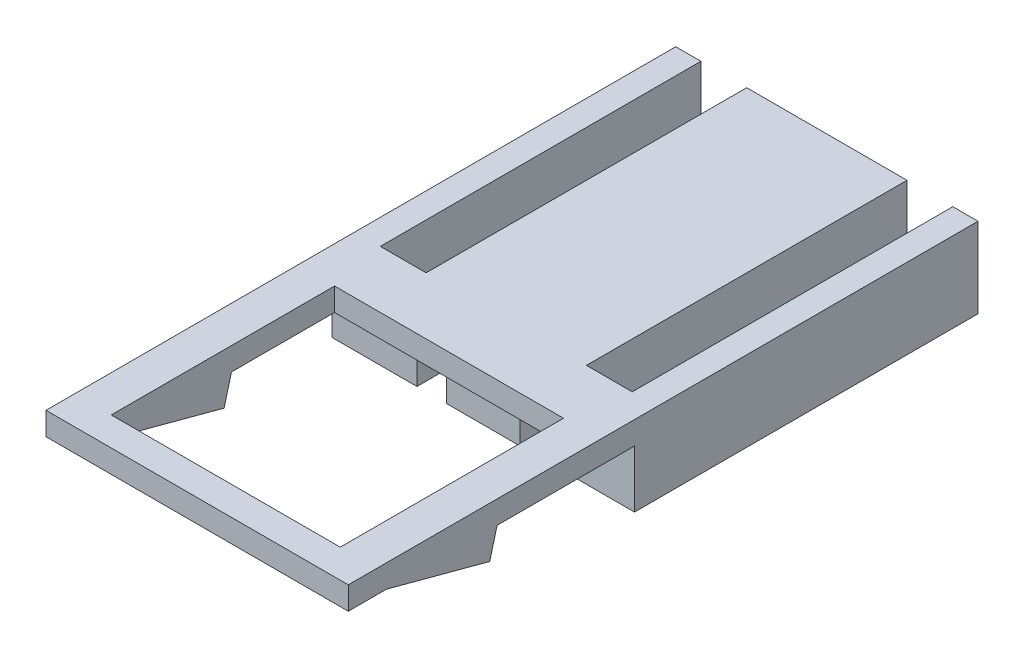
SolidWorks part; units mm, degrees
ref_plane "Front Plane" through (0, 0, 0) normal (0, 0, 1) x (1, 0, 0)
ref_plane "Top Plane" through (0, 0, 0) normal (0, 1, 0) x (1, 0, 0)
ref_plane "Right Plane" through (0, 0, 0) normal (1, 0, 0) x (0, 0, -1)
sketch "Sketch1" plane through (0, 0, 0) normal (0, 1, 0) x (1, 0, 0)
  line L1 (-31.75, 35) -> (31.75, 35)
  line L2 (-31.75, 35) -> (-31.75, 0)
  line L3 (-31.75, 0) -> (31.75, 0)
  line L4 (31.75, 35) -> (31.75, 0)
extrude "Boss-Extrude1" add sketch "Sketch1" along normal blind 12
sketch "Sketch3" plane through (0, 0, 0) normal (0, -1, 0) x (1, 0, 0)
  line L0 (-31.75, 0) -> (31.75, 0) construction
  line L1 (-13.2, 0) -> (13.2, 0)
  line L2 (-13.2, 0) -> (-13.2, -35)
  line L3 (-13.2, -35) -> (13.2, -35)
  line L4 (13.2, 0) -> (13.2, -35)
  line L5 (31.75, -35) -> (-31.75, -35) construction
extrude "Cut-Extrude2" cut sketch "Sketch3" against normal blind 5
sketch "Sketch4" plane through (0, 5, 0) normal (0, -1, 0) x (1, 0, 0)
  line L0 (13.2, 0) -> (-13.2, 0) construction
  line L1 (-5.8, 0) -> (-3.2, 0)
  line L2 (-5.8, 0) -> (-5.8, -35)
  line L3 (-5.8, -35) -> (-3.2, -35)
  line L4 (-3.2, 0) -> (-3.2, -35)
  line L5 (-13.2, -35) -> (13.2, -35) construction
  line L7 (3.2, 0) -> (5.8, 0)
  line L8 (3.2, 0) -> (3.2, -35)
  line L9 (3.2, -35) -> (5.8, -35)
  line L10 (5.8, 0) -> (5.8, -35)
extrude "Cut-Extrude3" cut sketch "Sketch4" against normal blind 3.5
sketch "Sketch5" plane through (0, 0, 0) normal (0, -1, 0) x (1, 0, 0)
  line L1 (-31.75, -35) -> (-13.2, -35)
  line L2 (-31.75, -35) -> (-31.75, 0)
  line L3 (-31.75, 0) -> (-13.2, 0)
  line L4 (-13.2, -35) -> (-13.2, 0)
extrude "Cut-Extrude4" cut sketch "Sketch5" against normal through all
sketch "Sketch6" plane through (0, 0, 0) normal (0, -1, 0) x (1, 0, 0)
  line L1 (13.2, 0) -> (31.75, 0)
  line L2 (13.2, 0) -> (13.2, -35)
  line L3 (13.2, -35) -> (31.75, -35)
  line L4 (31.75, 0) -> (31.75, -35)
extrude "Cut-Extrude5" cut sketch "Sketch6" against normal through all
sketch "Sketch7" plane through (0, 0, 0) normal (0, 0, 1) x (1, 0, 0)
  line L0 (-13.2, 12) -> (13.2, 12) construction
  line L1 (-11, 12) -> (-7, 12)
  line L2 (-11, 12) -> (-11, 7)
  line L3 (-11, 7) -> (-7, 7)
  line L4 (-7, 12) -> (-7, 7)
extrude "Cut-Extrude6" cut sketch "Sketch7" against normal through all
sketch "Sketch8" plane through (0, 0, 0) normal (0, 0, 1) x (1, 0, 0)
  line L0 (-7, 12) -> (13.2, 12) construction
  line L1 (11, 12) -> (7, 12)
  line L2 (11, 12) -> (11, 7)
  line L3 (11, 7) -> (7, 7)
  line L4 (7, 12) -> (7, 7)
extrude "Cut-Extrude7" cut sketch "Sketch8" against normal through all
sketch "Sketch12" plane through (0, 0, 0) normal (0, 0, 1) x (1, 0, 0)
  line L0 (13.2, 12) -> (13.2, 5) construction
  line L1 (-13.2, 5) -> (13.2, 5)
  line L2 (-13.2, 5) -> (-13.2, 15)
  line L3 (-13.2, 15) -> (13.2, 15)
  line L4 (13.2, 5) -> (13.2, 15)
extrude "Boss-Extrude2" add sketch "Sketch12" along normal blind 27
sketch "Sketch13" plane through (0, 15, 0) normal (0, 1, 0) x (1, 0, 0)
  line L1 (10, -5) -> (-10, -5)
  line L2 (10, -5) -> (10, -24.5)
  line L3 (10, -24.5) -> (-10, -24.5)
  line L4 (-10, -5) -> (-10, -24.5)
extrude "Cut-Extrude8" cut sketch "Sketch13" against normal through all
sketch "Sketch14" plane through (-13.2, 0, 0) normal (-1, 0, 0) x (0, 0, 1)
  line L1 (0, 12) -> (27, 12)
  line L2 (0, 12) -> (0, 15)
  line L3 (0, 15) -> (27, 15)
  line L4 (27, 12) -> (27, 15)
extrude "Cut-Extrude9" cut sketch "Sketch14" against normal through all
sketch "Sketch18" plane through (0, 0, 0) normal (0, 0, -1) x (-1, 0, 0)
  line L1 (3.2, 8.5) -> (5.8, 8.5)
  line L2 (3.2, 8.5) -> (3.2, 5)
  line L3 (3.2, 5) -> (5.8, 5)
  line L4 (5.8, 8.5) -> (5.8, 5)
  line L5 (-5.8, 8.5) -> (-3.2, 8.5)
  line L6 (-5.8, 8.5) -> (-5.8, 5)
  line L7 (-5.8, 5) -> (-3.2, 5)
  line L8 (-3.2, 8.5) -> (-3.2, 5)
extrude "Cut-Extrude12" cut sketch "Sketch18" against normal through all
sketch "Sketch19" plane through (-13.2, 0, 0) normal (-1, 0, 0) x (0, 0, 1)
  line L0 (27, 5) -> (-35, 5) construction
  line L1 (4, 5) -> (14, 5)
  line L2 (4, 5) -> (4, 10)
  line L3 (4, 10) -> (14, 10)
  line L4 (14, 5) -> (14, 10)
extrude "Cut-Extrude13" cut sketch "Sketch19" against normal through all
sketch "Sketch20" plane through (-13.2, 0, 0) normal (-1, 0, 0) x (0, 0, 1)
  line L0 (27, 12) -> (27, 5) construction
  line L1 (27, 10) -> (24.5, 10)
  line L2 (27, 10) -> (27, 5)
  line L3 (27, 5) -> (24.5, 5)
  line L4 (24.5, 10) -> (24.5, 5)
  line L5 (27, 5) -> (14, 5) construction
extrude "Cut-Extrude14" cut sketch "Sketch20" against normal through all
sketch "Sketch21" plane through (-13.2, 0, 0) normal (-1, 0, 0) x (0, 0, 1)
  line L0 (14, 10) -> (14.647, 7.5852)
  line L1 (14.647, 7.5852) -> (23.6593, 10)
  line L2 (24.5, 10) -> (24.5, 5)
  line L3 (24.5, 5) -> (14, 5)
  line L4 (14, 5) -> (14, 10)
  line L5 (23.6593, 10) -> (24.5, 10)
extrude "Cut-Extrude15" cut sketch "Sketch21" against normal through all
sketch "Sketch24" plane through (0, 5, 0) normal (0, -1, 0) x (1, 0, 0)
  line L0 (13.2, -35) -> (13.2, 4) construction
  line L1 (-13.2, 4) -> (13.2, 4)
  line L2 (-13.2, 4) -> (-13.2, 2)
  line L3 (-13.2, 2) -> (13.2, 2)
  line L4 (13.2, 4) -> (13.2, 2)
extrude "Cut-Extrude18" cut sketch "Sketch24" against normal blind 5
sketch "Sketch25" plane through (0, 12, 0) normal (0, 1, 0) x (1, 0, 0)
  line L0 (-13.2, 35) -> (-13.2, -27) construction
  line L1 (13.2, 35) -> (-13.2, 35)
  line L2 (13.2, 35) -> (13.2, 28)
  line L3 (13.2, 28) -> (-13.2, 28)
  line L5 (-13.2, 35) -> (-13.2, 28)
extrude "Cut-Extrude19" cut sketch "Sketch25" against normal through all
